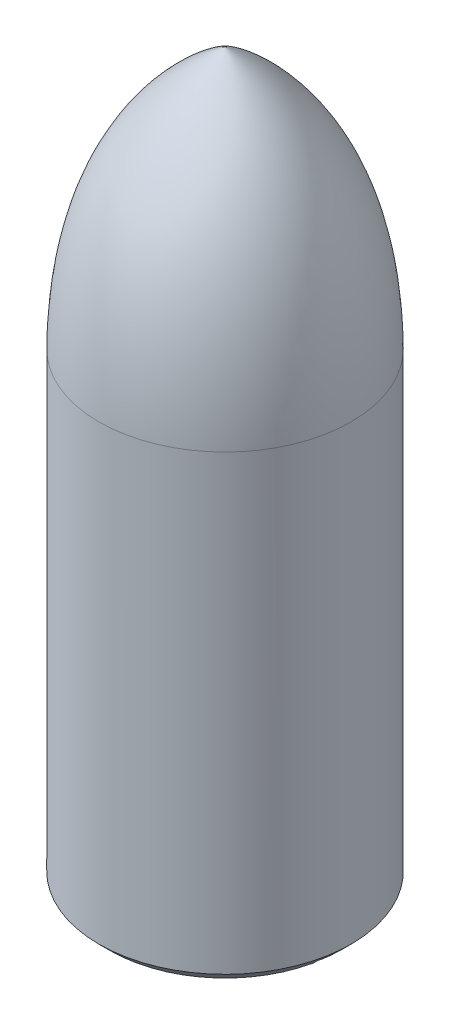
SolidWorks part; units mm, degrees
ref_plane "Front Plane" through (0, 0, 0) normal (0, 0, 1) x (1, 0, 0)
ref_plane "Top Plane" through (0, 0, 0) normal (0, 1, 0) x (1, 0, 0)
ref_plane "Right Plane" through (0, 0, 0) normal (1, 0, 0) x (0, 0, -1)
sketch "Sketch1" plane through (0, 0, 0) normal (0, 1, 0) x (1, 0, 0)
  line L1 (31.5, -6.5) -> (-31.5, -6.5)
  line L2 (31.5, -6.5) -> (31.5, 6.5)
  line L3 (31.5, 6.5) -> (-31.5, 6.5)
  line L4 (-31.5, -6.5) -> (-31.5, 6.5)
  line L5 (31.5, -6.5) -> (-31.5, 6.5) construction
  line L6 (31.5, 6.5) -> (-31.5, -6.5) construction
  circle A0 centre (0, 0) radius 34
  circle A1 centre (0, 0) radius 26.5
  dimension "D1" = 68
  dimension "D2" = 53
  dimension "D3" = 13
  dimension "D4" = 63
extrude "Boss-Extrude1" add sketch "Sketch1" along normal blind 125 contours A0 A1 L3 L2 L1 L4 region at (-33.0383, 0, 0)
sketch "Sketch2" plane through (0, 0, 0) normal (0, 0, 1) x (1, 0, 0)
  line L0 (0, 125) -> (0, 195.6389)
  line L1 (34, 125) -> (-34, 125) construction
  line L3 (0, 125) -> (34, 125)
  spline S0 degree 2 poles (0, 195.6389) (33.4978, 174.9908) (34, 125) knots 0 0 0 1 1 1
  dimension "D1" = 34
revolve "Revolve1" add sketch "Sketch2" angle 360 about L0
chamfer "Chamfer1" distance 3 angle 45 1 edges at (0, 0, 34)
